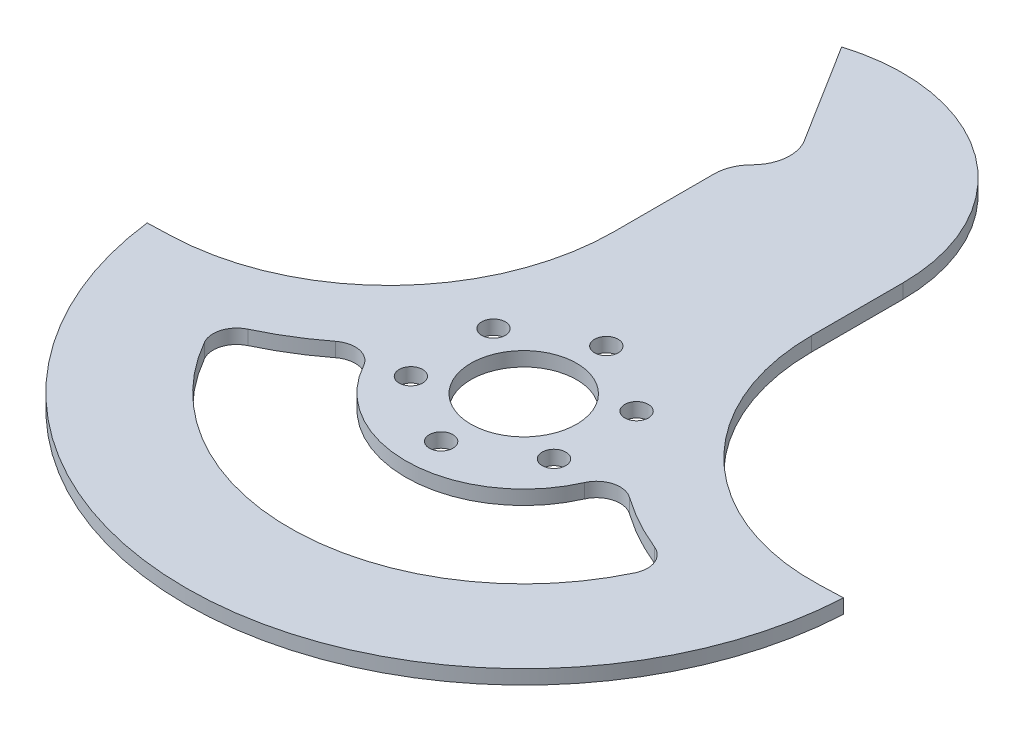
SolidWorks part; units mm, degrees
ref_plane "Front Plane" through (0, 0, 0) normal (0, 0, 1) x (1, 0, 0)
ref_plane "Top Plane" through (0, 0, 0) normal (0, 1, 0) x (1, 0, 0)
ref_plane "Right Plane" through (0, 0, 0) normal (1, 0, 0) x (0, 0, -1)
other "Center of Mass"
sketch "Sketch1" plane through (0, 0, 0) normal (0, 1, 0) x (1, 0, 0)
  line L0 (0, 0) -> (-23040.0357, 36803.9862) construction
  line L1 (0, -1000) -> (0, 49000) construction
  line L2 (-29.7853, 97.136) -> (-16.5198, 75.9457)
  line L3 (18.7342, 112.0138) -> (41531.855, 12841.4067) construction
  line L4 (-20, 60.3286) -> (20, 60.3286) construction
  line L5 (-20, 60.3286) -> (-20, 39.1549)
  line L6 (20, 60.3286) -> (20, 40.9875)
  line L7 (0, 0) -> (-71.0663, -8.7258) construction
  line L8 (0, 0) -> (71.5019, -3.7473) construction
  line L9 (-71.0663, -8.7258) -> (71.5019, -3.7473) construction
  line L10 (-71.0663, -8.7258) -> (-66.0694, -8.5513)
  line L11 (71.5019, -3.7473) -> (66.5049, -3.9218)
  line L12 (-28.8426, 54.8122) -> (35326.4965, 35410.1512) construction
  circle A0 centre (0, 0) radius 101.6 construction
  arc A1 (-16.5198, 75.9457) -> (-17.6481, 66.0067) centre (-23.3262, 71.6848) cw
  arc A2 (-17.6481, 66.0067) -> (-20, 60.3286) centre (-11.97, 60.3286) ccw
  arc A3 (-29.7853, 97.136) -> (20, 60.3286) centre (-18.4989, 60.3286) cw
  circle A4 centre (0, 0) radius 71.6 construction
  arc A5 (-71.0663, -8.7258) -> (71.5019, -3.7473) centre (0, 0) ccw
  arc A6 (-66.0694, -8.5513) -> (-20, 39.1549) centre (-67.7353, 39.1549) ccw
  arc A7 (20, 40.9875) -> (66.5049, -3.9218) centre (64.9367, 40.9875) ccw
  circle A8 centre (0, 0) radius 30.5026 construction
  point P9 (0, 60.3286)
  point P20 (0, -71.6)
  point P21 (0, -101.6)
  point P31 (2.4988, -71.5564)
  point P34 (-15.2961, 71.6848)
  dimension "D1" = 203.2
  dimension "D2" = 75
  dimension "D3" = 25
  dimension "D4" = 40
  dimension "D5" = 30
  dimension "D6" = 92
  dimension "D7" = 170
  dimension "D8" = 5
  dimension "D9" = 45
extrude "Boss-Extrude1" add sketch "Sketch1" along normal blind 3.02
sketch "Sketch6" plane through (0, 3.02, 0) normal (0, 1, 0) x (1, 0, 0)
  line L0 (-41.0794, -17.6358) -> (-47.4528, -4.0572) construction
  line L1 (29.2213, -7.1458) -> (38.1596, 4.9002) construction
  arc A0 (-45.5884, -19.5412) -> (46.8909, -16.168) centre (0, 0) ccw
  arc A1 (-16.623, 2.7783) -> (-45.5884, -19.5412) centre (-67.7353, 39.1549) cw
  arc A2 (14.252, 8.9958) -> (46.8909, -16.168) centre (64.9367, 40.9875) ccw
  arc A3 (-16.623, 2.7783) -> (14.252, 8.9958) centre (0, 0) ccw
  arc A4 (-66.0694, -8.5513) -> (-20, 39.1549) centre (-67.7353, 39.1549) ccw construction
  arc A5 (-71.0663, -8.7258) -> (71.5019, -3.7473) centre (0, 0) ccw construction
  arc A6 (20, 40.9875) -> (66.5049, -3.9218) centre (64.9367, 40.9875) ccw construction
  circle A7 centre (0, 0) radius 30.5026 construction
  point P23 (0, -49.6)
  dimension "D1" = 22
  dimension "D2" = 15
extrude "Cut-Extrude2" cut sketch "Sketch6" against normal through all
fillet "Fillet6" radius 5 2 edges at (46.8909, 1.51, 16.168) (-45.5884, 1.51, 19.5412)
sketch "Sketch7" plane through (0, 3.02, 0) normal (0, 1, 0) x (1, 0, 0)
  circle A0 centre (0, 0) radius 25
  dimension "D1" = 50
extrude "Boss-Extrude5" add sketch "Sketch7" against normal up to surface (3.02 mm away) up to face at (0.9289, 0, 19.6333)
fillet "Fillet7" radius 5 2 edges at (24.7558, 1.51, 3.486) (-24.2527, 1.51, 6.0666)
sketch "Sketch8" plane through (0, 3.02, 0) normal (0, 1, 0) x (1, 0, 0)
  circle A0 centre (0.1682, -0.1726) radius 11.2
  dimension "D1" = 22.4
extrude "Cut-Extrude3" cut sketch "Sketch8" against normal through all
sketch "Sketch10" plane through (0, 3.02, 0) normal (0, 1, 0) x (1, 0, 0)
  circle A0 centre (0.1682, -17.6726) radius 7.3266 construction
  circle A1 centre (0, 0) radius 25 construction
  circle A3 centre (0.1682, -17.6726) radius 2.5
  circle A4 centre (-14.9873, -8.9226) radius 2.5
  circle A5 centre (-14.9873, 8.5774) radius 2.5
  circle A6 centre (0.1682, 17.3274) radius 2.5
  circle A7 centre (15.3236, 8.5774) radius 2.5
  circle A8 centre (15.3236, -8.9226) radius 2.5
  point P21 (0.1682, -0.1726)
  dimension "D1" = 5
  dimension "D3" = 35
  dimension "D2" = 6
extrude "Cut-Extrude4" cut sketch "Sketch10" against normal through all
sketch "Sketch11" plane through (0, 0, 0) normal (0, 1, 0) x (1, 0, 0)
  circle A0 centre (0.1682, -0.1726) radius 101.8143 construction
  circle A1 centre (0.1682, -0.1726) radius 11.2 construction
  circle A2 centre (0.1682, -0.1726) radius 71.7461 construction
ref_axis "Axis1" through (0.1682, 0, 0.1726) along (0, 1, 0)
